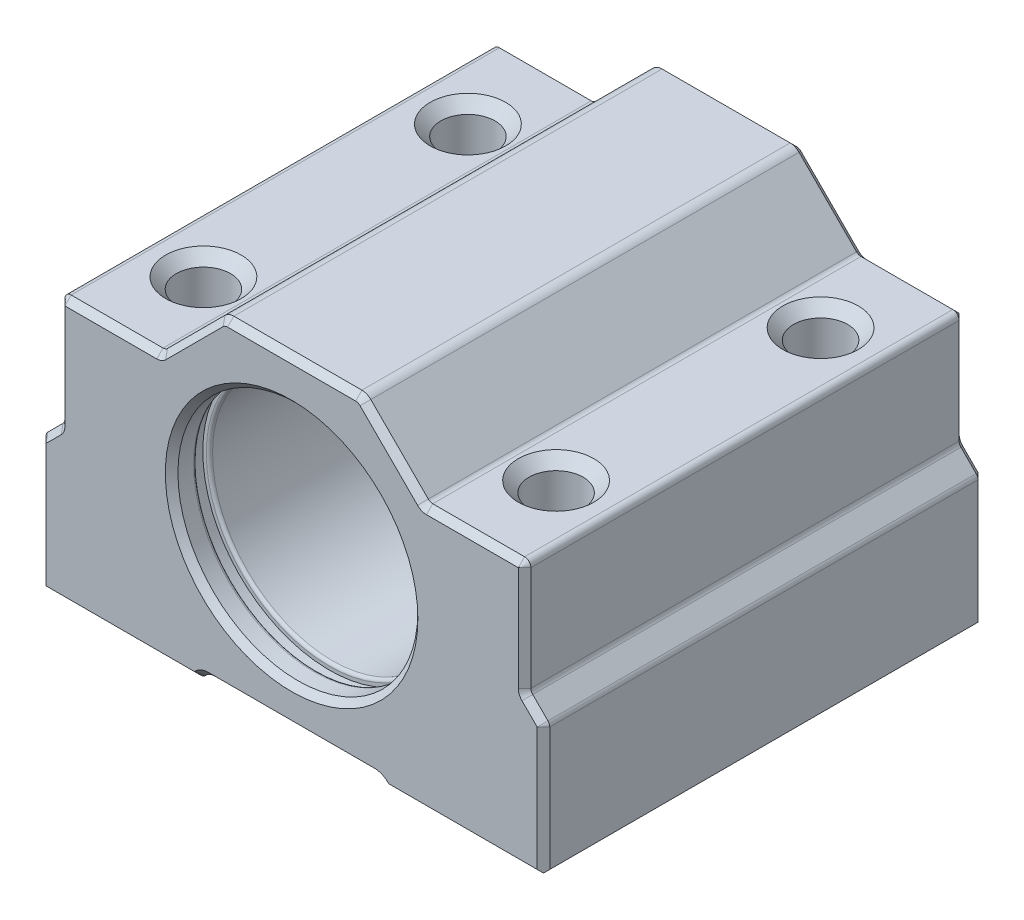
SolidWorks part; units mm, degrees
ref_plane "Front Plane" through (0, 0, 0) normal (0, 0, 1) x (1, 0, 0)
ref_plane "Top Plane" through (0, 0, 0) normal (0, 1, 0) x (1, 0, 0)
ref_plane "Right Plane" through (0, 0, 0) normal (1, 0, 0) x (0, 0, -1)
sketch "Sketch1" plane through (0, 0, 0) normal (0, 0, 1) x (1, 0, 0)
  line L0 (0, 25.4984) -> (0, -16.7663) construction
  line L1 (18.6464, -1.1464) -> (19.8536, -2.3536)
  line L2 (20, -12.5) -> (20, -2.7071)
  line L4 (18.5, -0.7929) -> (18.5, 7.5)
  line L5 (18, 8) -> (10.7071, 8)
  line L6 (10.3536, 8.1464) -> (5.7929, 12.7071)
  line L7 (5.0858, 13) -> (-5.0858, 13)
  line L8 (-6.5858, -12.5) -> (6.5858, -12.5)
  line L17 (7.2929, -12.7929) -> (7.3536, -12.8536)
  line L27 (7.7071, -13) -> (19.5, -13)
  line L28 (19.5, -13) -> (20, -12.5)
  line L29 (-19.5, -13) -> (-20, -12.5)
  line L30 (-7.7071, -13) -> (-19.5, -13)
  line L31 (-7.2929, -12.7929) -> (-7.3536, -12.8536)
  line L32 (-10.3536, 8.1464) -> (-5.7929, 12.7071)
  line L33 (-18, 8) -> (-10.7071, 8)
  line L34 (-18.5, -0.7929) -> (-18.5, 7.5)
  line L35 (-20, -12.5) -> (-20, -2.7071)
  line L36 (-18.6464, -1.1464) -> (-19.8536, -2.3536)
  circle A0 centre (0, 0) radius 5 construction
  circle A6 centre (0, 0) radius 9.525
  arc A7 (6.5858, -12.5) -> (7.2929, -12.7929) centre (6.5858, -13.5) cw
  arc A9 (5.0858, 13) -> (5.7929, 12.7071) centre (5.0858, 12) cw
  arc A12 (20, -2.7071) -> (19.8536, -2.3536) centre (19.5, -2.7071) ccw
  arc A13 (18.6464, -1.1464) -> (18.5, -0.7929) centre (19, -0.7929) cw
  arc A15 (18, 8) -> (18.5, 7.5) centre (18, 7.5) cw
  arc A17 (10.7071, 8) -> (10.3536, 8.1464) centre (10.7071, 8.5) cw
  arc A19 (7.7071, -13) -> (7.3536, -12.8536) centre (7.7071, -12.5) cw
  arc A21 (-7.7071, -13) -> (-7.3536, -12.8536) centre (-7.7071, -12.5) ccw
  arc A22 (-10.7071, 8) -> (-10.3536, 8.1464) centre (-10.7071, 8.5) ccw
  arc A23 (-18, 8) -> (-18.5, 7.5) centre (-18, 7.5) ccw
  arc A24 (-18.6464, -1.1464) -> (-18.5, -0.7929) centre (-19, -0.7929) ccw
  arc A25 (-20, -2.7071) -> (-19.8536, -2.3536) centre (-19.5, -2.7071) cw
  arc A26 (-5.0858, 13) -> (-5.7929, 12.7071) centre (-5.0858, 12) ccw
  arc A27 (-6.5858, -12.5) -> (-7.2929, -12.7929) centre (-6.5858, -13.5) ccw
  point P7 (0, 13)
  point P9 (-20, -13)
  point P12 (0, -12.5)
  point P13 (0, 13)
  point P15 (0, 13)
  point P18 (18.5, 8)
  point P28 (18.5, -1)
  point P30 (7, -12.5)
  point P35 (10.5, 8)
  point P39 (5.5, 13)
  point P48 (20, -2.5)
  point P51 (18.5, -1)
  point P58 (18.5, 8)
  point P64 (10.5, 8)
  point P65 (0, -12.5)
  point P66 (0, -12.5)
  point P67 (-7.5, -13)
  point P68 (-10.5, 8)
  point P71 (7.5, -13)
  point P72 (-18.5, 8)
  point P73 (-18.5, -1)
  point P74 (-20, -2.5)
  point P75 (-5.5, 13)
  point P76 (-7, -12.5)
  point P78 (20, -13)
  dimension "D1" = 10
  dimension "D9" = 19.8536
  dimension "D2" = 19.05
  dimension "D3" = 1
  dimension "D4" = 0.5
  dimension "D5" = 5.0858
  dimension "D7" = 10.3536
  dimension "D6" = 6.5858
  dimension "D8" = 18.5
  dimension "D10" = 8.5
  dimension "D11" = 1
  dimension "D12" = 12.7929
extrude "Boss-Extrude1" add sketch "Sketch1" along normal blind 35
chamfer "Chamfer2" distance 0.5 angle 45 2 edges at (-9.525, 0, 0) (-9.525, 0, 35)
sketch "Sketch2" plane through (0, 0, 0) normal (1, 0, 0) x (0, 0, -1)
  line L0 (0, 0) -> (-40.0609, 0) construction
  line L2 (-33, -9.5) -> (-32, -9.5)
  line L3 (-33, -9.5) -> (-33, -10.05)
  line L4 (-33, -10.05) -> (-32, -10.05)
  line L5 (-32, -9.5) -> (-32, -10.05)
  line L6 (-3, -9.5) -> (-2, -9.5)
  line L7 (-3, -9.5) -> (-3, -10.05)
  line L8 (-3, -10.05) -> (-2, -10.05)
  line L9 (-2, -9.5) -> (-2, -10.05)
  line L11 (0, -10.025) -> (0, 10.025) construction
  line L12 (-35, 10.025) -> (-35, -10.025) construction
  line L13 (0, -10.025) -> (0, 10.025) construction
  line L14 (-35, 10.025) -> (-35, -10.025) construction
  dimension "D1" = 9.5
  dimension "D2" = 9.5
  dimension "D5" = 1
  dimension "D6" = 1
  dimension "D7" = 0.55
  dimension "D8" = 0.55
  dimension "D3" = 2
  dimension "D4" = 29
revolve "Cut-Revolve1" cut sketch "Sketch2" angle 360 about L0
fillet "Fillet2" radius 0.25 4 edges at (9.525, 0, 2) (-9.525, 0, 3) (-9.525, 0, 33) (9.525, 0, 32)
hole_wizard "M5x0.8 Tapped Hole1" positions "Sketch4" profile "Sketch5" tap size "M5x0.8" standard "ANSI Metric" end condition through all
sketch "Sketch4" plane through (0, -13, 0) normal (0, -1, 0) x (-1, 0, 0)
  point P0 (14, -28)
  point P3 (14, -7)
  point P6 (-14, -7)
  point P9 (-14, -28)
  dimension "D1" = 14
  dimension "D2" = 14
  dimension "D3" = 14
  dimension "D4" = 14
  dimension "D5" = 21
  dimension "D6" = 21
  dimension "D7" = 7
  dimension "D8" = 7
sketch "Sketch5" plane through (-14, -13, 28) normal (1, 0, 0) x (0, 0, -1)
  line L0 (0, 0) -> (0, 21)
  line L1 (0, 21) -> (3, 21)
  line L2 (2.15, 20.15) -> (2.15, 1.35)
  line L3 (2.15, 1.35) -> (3.5, 0)
  line L5 (3.5, 0) -> (0, 0)
  line L6 (-2.15, 1.35) -> (-3.5, 0) construction
  line L7 (3, 21) -> (2.15, 20.15)
  line L8 (-3, 21) -> (-2.15, 20.15) construction
  line L11 (0, -6.35) -> (0, 107.95) construction
  dimension "Thru Tap Drill Dia." = 4.3
  dimension "Thru Tap Drill Depth" = 21
  dimension "Near C'Sink Dia." = 7
  dimension "Near C'Sink Angle" = 90
  dimension "Far C'Sink Dia." = 6
  dimension "Far C'Sink Angle" = 90
cosmetic thread "Hole Thread9" parameters "D1"=12, "D2"=5
cosmetic thread "Hole Thread10" parameters "D1"=12, "D2"=5
cosmetic thread "Hole Thread11" parameters "D1"=12, "D2"=5
cosmetic thread "Hole Thread12" parameters "D1"=12, "D2"=5
chamfer "Chamfer3" distance 0.5 angle 45 60 edges at (0, -12.5, 0) (0, 13, 0) (20, -7.6036, 0) (8.0732, 10.4268, 0) (19.25, -1.75, 0) (14.3536, 8, 0) (18.5, 3.3536, 0) (18.5, 3.3536, 35) (19.25, -1.75, 35) (14.3536, 8, 35) (20, -7.6036, 35) (8.0732, 10.4268, 35) (0, 13, 35) (0, -12.5, 35) (-20, -7.6036, 0) (-19.9619, -2.5158, 0) (-19.25, -1.75, 0) (-18.5381, -0.9842, 0) (-18.5, 3.3536, 0) (-18.3536, 7.8536, 0) (-14.3536, 8, 0) (-10.5158, 8.0381, 0) (-8.0732, 10.4268, 0) (-5.4685, 12.9239, 0) (5.4685, 12.9239, 0) (19.9619, -2.5158, 0) (10.5158, 8.0381, 0) (18.5381, -0.9842, 0) (18.3536, 7.8536, 0) (-13.6036, -13, 0) (-7.5158, -12.9619, 0) (-7.3232, -12.8232, 0) (-6.9685, -12.5761, 0) (6.9685, -12.5761, 0) (7.3232, -12.8232, 0) (7.5158, -12.9619, 0) (13.6036, -13, 0) (-13.6036, -13, 35) (-7.5158, -12.9619, 35) (-7.3232, -12.8232, 35) (-6.9685, -12.5761, 35) (6.9685, -12.5761, 35) (7.3232, -12.8232, 35) (7.5158, -12.9619, 35) (13.6036, -13, 35) (19.9619, -2.5158, 35) (18.5381, -0.9842, 35) (18.3536, 7.8536, 35) (10.5158, 8.0381, 35) (-20, -7.6036, 35) (5.4685, 12.9239, 35) (-19.9619, -2.5158, 35) (-19.25, -1.75, 35) (-5.4685, 12.9239, 35) (-18.5381, -0.9842, 35) (-8.0732, 10.4268, 35) (-18.5, 3.3536, 35) (-10.5158, 8.0381, 35) (-18.3536, 7.8536, 35) (-14.3536, 8, 35)
equation "\"D2@Sketch2\"=\"D1@Sketch2\""
equation "\"D8@Sketch2\"=\"D7@Sketch2\""
equation "\"D6@Sketch2\"=\"D5@Sketch2\""
equation "\"D2@Sketch4\"=\"D1@Sketch4\""
equation "\"D3@Sketch4\"=\"D1@Sketch4\""
equation "\"D4@Sketch4\"=\"D1@Sketch4\""
equation "\"D7@Sketch4\"=(35-\"D5@Sketch4\")/2"
equation "\"D6@Sketch4\"=\"D5@Sketch4\""
equation "\"D8@Sketch4\"=\"D7@Sketch4\""
